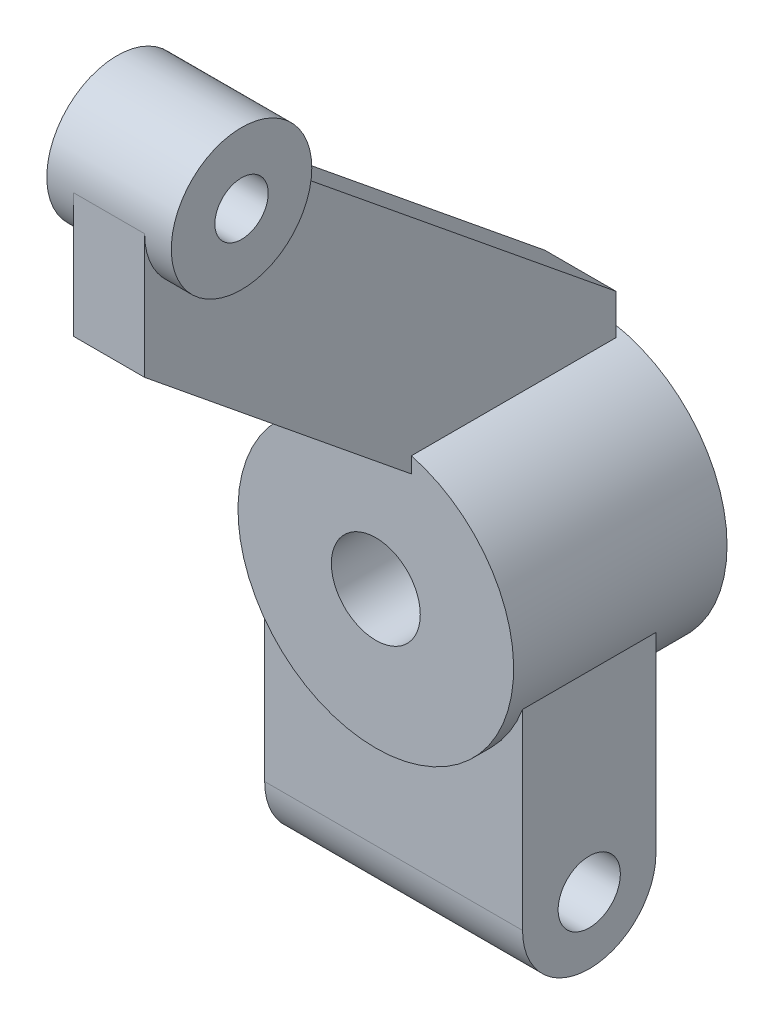
SolidWorks part; units mm, degrees
ref_plane "Front Plane" through (0, 0, 0) normal (0, 0, 1) x (1, 0, 0)
ref_plane "Top Plane" through (0, 0, 0) normal (0, 1, 0) x (1, 0, 0)
ref_plane "Right Plane" through (0, 0, 0) normal (1, 0, 0) x (0, 0, -1)
sketch "Sketch1" plane through (0, 0, 0) normal (0, 0, 1) x (1, 0, 0)
  circle A0 centre (0, 0) radius 7.75
  dimension "D1" = 15.5
extrude "Main Cylinder" add sketch "Sketch1" along normal blind 12 contours A0
sketch "Sketch2" plane through (0, 0, 0) normal (1, 0, 0) x (0, 0, -1)
  line L0 (-3.5, -2.0139) -> (-3.5, -13.5)
  line L1 (-3.5, -2.0139) -> (-11, -2.0139)
  line L2 (-11, -2.0139) -> (-11, -13.5)
  line L3 (0, 7.75) -> (-12, 7.75) construction
  line L5 (-12, 7.75) -> (-12, -7.75) construction
  arc A0 (-3.5, -13.5) -> (-11, -13.5) centre (-7.25, -13.5) cw
  point P5 (-7.25, -17.25)
  dimension "D1" = 3.75
  dimension "D2" = 25
  dimension "D3" = 1
extrude "Drop" add sketch "Sketch2" along normal mid plane 14.5
sketch "Sketch3" plane through (0, 0, 0) normal (1, 0, 0) x (0, 0, -1)
  line L0 (-27, 18.8054) -> (-27, 25.8)
  line L2 (-19.191, 24.9569) -> (-0.5, 9.75)
  line L3 (-0.5, 9.75) -> (-0.5, 5.606)
  line L4 (0, -7.75) -> (0, 7.75) construction
  line L5 (-0.5, 5.606) -> (-12, 5.606)
  line L6 (-12, 7.75) -> (-12, -7.75) construction
  line L7 (-12, 5.606) -> (-12, 6.6015)
  line L8 (-12, 6.6015) -> (-27, 18.8054)
  arc A0 (-11, -13.5) -> (-3.5, -13.5) centre (-7.25, -13.5) ccw construction
  arc A1 (-27, 25.8) -> (-19.191, 24.9569) centre (-23.05, 25.8) cw
  point P16 (-7.25, -17.25)
  point P26 (-22.626, 29.7272)
  dimension "D4" = 3.95
  dimension "D5" = 47
  dimension "D1" = 9.7
  dimension "D2" = 27
  dimension "D3" = 27
  dimension "D6" = 10.9218
  dimension "D7" = 0.5
extrude "Riser" add sketch "Sketch3" along normal mid plane 4
sketch "Sketch5" plane through (0, 0, 0) normal (1, 0, 0) x (0, 0, -1)
  circle A0 centre (-23.05, 25.8) radius 3.95
  arc A1 (-19.191, 24.9569) -> (-27, 25.8) centre (-23.05, 25.8) ccw construction
extrude "Riser Boss" add sketch "Sketch5" along normal mid plane 7
sketch "Sketch6" plane through (3.5, 0, 0) normal (1, 0, 0) x (0, 0, -1)
  circle A0 centre (-23.05, 25.8) radius 1.5
  circle A1 centre (-23.05, 25.8) radius 3.95 construction
  dimension "D1" = 3
extrude "Top Holes" cut sketch "Sketch6" against normal through all and the other way through all
sketch "Sketch7" plane through (7.25, 0, 0) normal (1, 0, 0) x (0, 0, -1)
  circle A0 centre (-7.25, -13.5) radius 1.75
  arc A1 (-11, -13.5) -> (-3.5, -13.5) centre (-7.25, -13.5) ccw construction
  dimension "D1" = 3.5
extrude "Bottom Holes" cut sketch "Sketch7" against normal through all
sketch "Sketch8" plane through (0, 0, 0) normal (0, 0, -1) x (-1, 0, 0)
  circle A0 centre (0, 0) radius 2.5
  dimension "D1" = 5
extrude "Bearing Hole" cut sketch "Sketch8" against normal through all
